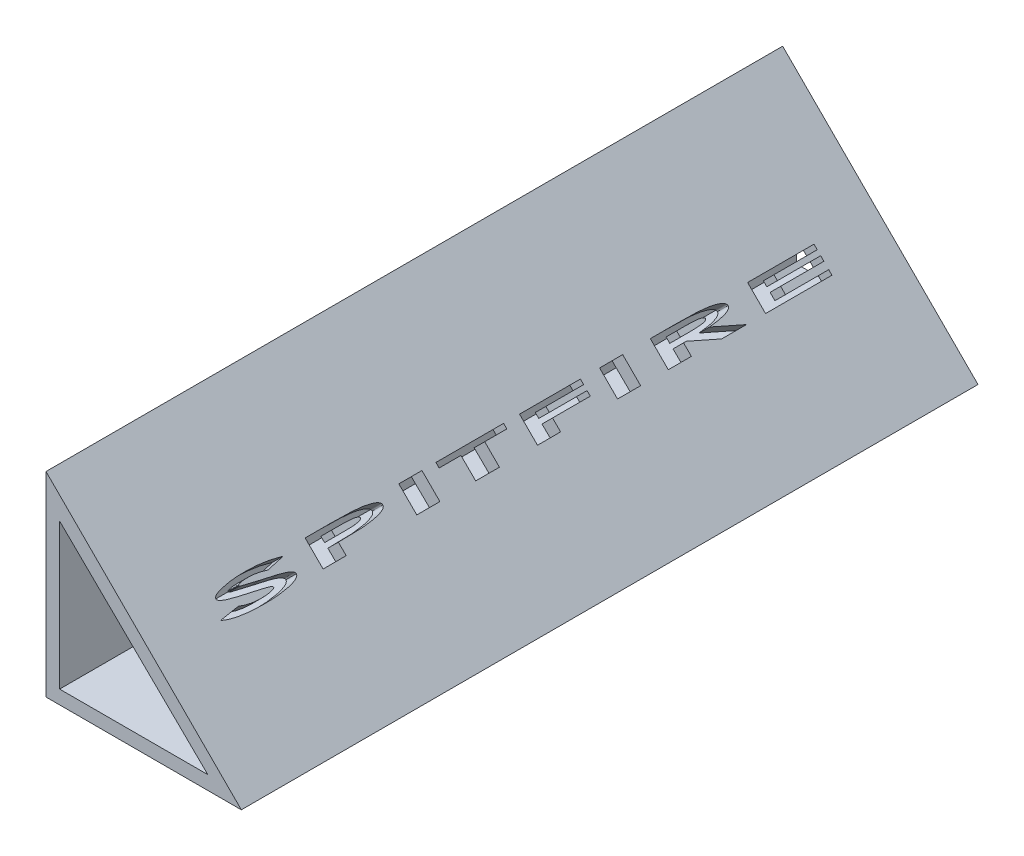
SolidWorks part; units mm, degrees
ref_plane "Front Plane" through (0, 0, 0) normal (0, 0, 1) x (1, 0, 0)
ref_plane "Top Plane" through (0, 0, 0) normal (0, 1, 0) x (1, 0, 0)
ref_plane "Right Plane" through (0, 0, 0) normal (1, 0, 0) x (0, 0, -1)
sketch "Sketch1" plane through (0, 0, 0) normal (0, 0, 1) x (1, 0, 0)
  line L0 (0, 0) -> (0, 26.9408)
  line L1 (0, 26.9408) -> (26.9408, 0)
  line L2 (26.9408, 0) -> (0, 0)
  line L3 (1.8809, 21.9579) -> (1.8809, 1.8909)
  line L4 (1.8809, 1.8909) -> (22.3209, 1.8909)
  line L5 (22.3209, 1.8909) -> (1.8809, 21.9579)
  dimension "D1" = 38.1
  dimension "D2" = 26.9408
  dimension "D3" = 26.9408
extrude "Boss-Extrude1" add sketch "Sketch1" along normal blind 101.6
sketch "Sketch2" plane through (13.4704, 13.4704, 0) normal (0.7071, 0.7071, 0) x (0, 0, -1)
  text T0 "<b>SPITFIRE</b>" font "Century Gothic" height 3.5
extrude "Cut-Extrude1" cut sketch "Sketch2" against normal blind 2.54
